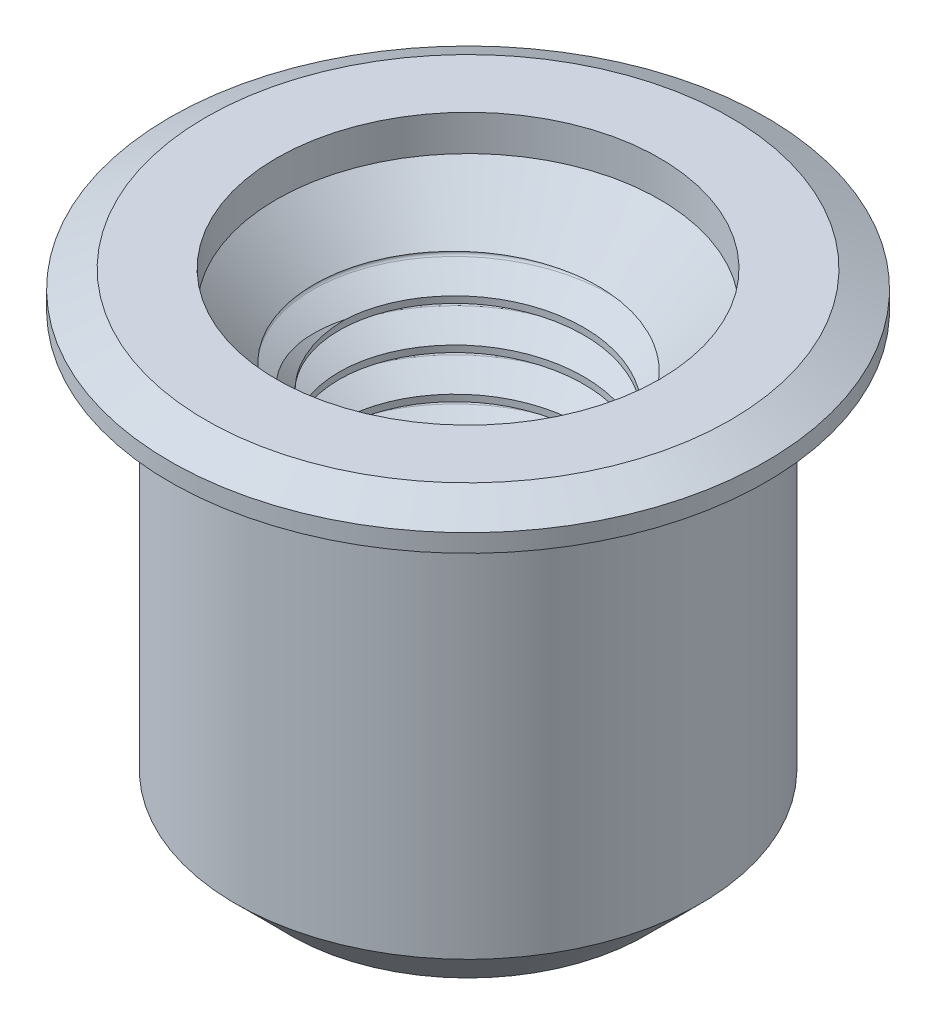
SolidWorks part; units mm, degrees
ref_plane "Front Plane" through (0, 0, 0) normal (0, 0, 1) x (1, 0, 0)
ref_plane "Top Plane" through (0, 0, 0) normal (0, 1, 0) x (1, 0, 0)
ref_plane "Right Plane" through (0, 0, 0) normal (1, 0, 0) x (0, 0, -1)
sketch "Sketch1" plane through (0, 0, 0) normal (0, 0, 1) x (1, 0, 0)
  line L0 (-4.953, -9.2415) -> (-3.7805, -10.414)
  line L1 (-4.0821, -0.762) -> (-2.608, -0.762) construction
  line L2 (-2.608, -0.762) -> (-2.608, -2.2361) construction
  line L3 (-3.7805, -10.414) -> (-3.175, -10.414)
  line L4 (6.35, 0) -> (5.588, 0) construction
  line L5 (-3.175, -10.414) -> (-2.608, -9.847)
  line L6 (6.35, -0.381) -> (6.35, 0) construction
  line L7 (-2.608, -9.847) -> (-2.608, -2.2361)
  line L8 (4.953, -10.414) -> (3.7805, -10.414) construction
  line L9 (-2.608, -2.2361) -> (-4.0821, -0.762)
  line L10 (2.608, -10.414) -> (2.608, -9.847) construction
  line L11 (-4.0821, -0.762) -> (-4.0821, 0)
  line L12 (4.953, -9.2415) -> (4.953, -10.414) construction
  line L13 (3.175, -10.414) -> (2.608, -10.414) construction
  line L14 (-4.0821, 0) -> (-5.588, 0)
  line L15 (-5.588, 0) -> (-6.35, -0.381)
  line L16 (6.35, -11.0998) -> (6.35, -1.4478) construction
  line L17 (-6.35, -0.381) -> (-6.35, -0.762)
  line L18 (6.35, -0.762) -> (4.953, -0.762) construction
  line L19 (-6.35, -0.762) -> (-4.953, -0.762)
  line L20 (-4.953, -0.762) -> (-4.953, -9.2415)
  line L21 (0, 0) -> (0, -10.414) construction
  line L22 (-6.35, -0.762) -> (-6.35, 0) construction
  line L23 (-6.35, 0) -> (-5.588, 0) construction
  line L24 (-4.953, -9.2415) -> (-4.953, -10.414) construction
  line L25 (-4.953, -10.414) -> (-3.7805, -10.414) construction
  line L26 (-3.175, -10.414) -> (-2.608, -10.414) construction
  line L27 (-2.608, -10.414) -> (-2.608, -9.847) construction
  line L28 (-2.608, -10.414) -> (0, -10.414) construction
  line L29 (6.35, -0.381) -> (6.35, -0.762) construction
  line L30 (-3.7805, -10.414) -> (-2.608, -10.414) construction
  line L32 (0, 0) -> (-4.0821, 0) construction
  dimension "D7" = 5.2161
  dimension "D8" = 45
  dimension "D12" = 9.652
  dimension "D2" = 8.1643
revolve "Revolve1" add sketch "Sketch1" angle 360 about L21
sketch "Sketch3" plane through (0, -10.414, 0) normal (0, -1, 0) x (1, 0, 0)
  circle A1 centre (0, 0) radius 3.175
  point P1 (3.175, 0)
  dimension "D1" = 6.35
ref_plane "Plane1" through (-4.953, 0, 0) normal (1, 0, 0) x (0, 0, -1)
sketch "Sketch2" plane through (-4.953, 0, 0) normal (1, 0, 0) x (0, 0, -1)
  line L0 (-4.953, -0.762) -> (4.953, -0.762) construction
  line L1 (-0.127, -0.762) -> (0.127, -0.762)
  line L2 (-0.127, -0.762) -> (-0.127, -0.254)
  line L3 (-0.127, -0.254) -> (0.127, -0.254) construction
  line L4 (0.127, -0.762) -> (0.127, -0.254)
  line L5 (0, -0.762) -> (0, 0) construction
  line L6 (-0.127, -0.254) -> (0, -0.762)
  line L7 (0, -0.762) -> (0.127, -0.254)
  line L8 (0, -0.254) -> (0, -0.762) construction
  line L10 (0, -0.762) -> (0, -0.254) construction
  line L11 (0, -0.508) -> (0, -0.254) construction
  dimension "D1" = 0.254
ref_axis "Axis1" through (0, 0, 0) along (0, -1, 0)
curve "Helix/Spiral1" pitch 0.9071 height 18.5388 radius 3.175 centre (0, -10.414, 0) axis (0, 1, 0) start towards (1, 0, 0) parameters "Height"=18.5388, "Pitch"=0.9071
sketch "Sketch4" plane through (0, 0, 0) normal (0, 0, 1) x (1, 0, 0)
  line L0 (2.4876, -10.0171) -> (2.4876, -10.9243) construction
  line L1 (2.4876, -10.9243) -> (3.2732, -10.4707) construction
  line L2 (2.4876, -10.0171) -> (3.2732, -10.4707) construction
  line L3 (2.5858, -10.0738) -> (2.5858, -10.8676) construction
  line L6 (2.4876, -10.4707) -> (2.5858, -10.4707) construction
  line L8 (3.175, -10.4707) -> (3.2732, -10.4707) construction
  line L9 (3.175, -10.414) -> (3.175, -10.5274) construction
  line L11 (2.5367, -10.0455) -> (2.5367, -10.8959)
  line L12 (2.5367, -10.8959) -> (3.175, -10.5274)
  line L14 (3.175, -10.414) -> (2.5367, -10.0455)
  arc A0 (3.175, -10.5274) -> (3.175, -10.414) centre (3.1423, -10.4707) ccw
  point P13 (2.5367, -10.4707)
  dimension "D1" = 0.9071
  dimension "D2" = 0.1134
sweep "Cut-Sweep1" cut profiles "Sketch4" path "Helix/Spiral1" align with end faces yes
ref_plane "Plane2" [suppressed] through (0, -2.794, 0) normal (0, -1, 0) x (1, 0, 0)
sketch "Sketch5" [suppressed] plane through (0, -2.794, 0) normal (0, -1, 0) x (1, 0, 0)
  circle A0 centre (0, 0) radius 3.429
  point P3 (-3.429, 0)
extrude "Extrude2" [suppressed] cut sketch "Sketch5" along normal blind 0.6858
pattern_linear "LPattern1" [suppressed] count 2 spacing 0.6858 along (0, 1, 0) of bodies 117
delete or keep bodies "Body-Delete1" [suppressed] type delete bodies bodies 117
combine bodies "Combine1" [suppressed] operation type add bodies to combine 118 119
sketch "Sketch6" [suppressed] plane through (0, 0, 0) normal (0, 0, 1) x (1, 0, 0)
  line L0 (-3.429, -2.794) -> (-2.8765, -2.794)
  line L1 (-2.8765, -2.794) -> (-2.8765, -4.318)
  line L2 (-2.8765, -4.318) -> (-3.429, -4.318)
  line L3 (-2.8765, -3.683) -> (-2.8765, 0) construction
  line L4 (-6.985, -2.794) -> (6.985, -2.794) construction
  line L5 (-3.429, -0.762) -> (-3.429, -10.5089) construction
  line L6 (0, 0) -> (0, -11.43) construction
  line L7 (0, 0) -> (0, -11.43) construction
  arc A0 (-3.429, -2.794) -> (-3.429, -4.318) centre (-3.429, -3.556) ccw
  dimension "D1" = 1.524
revolve "Revolve2" [suppressed] add sketch "Sketch6" angle 360 about L7
equation "\"Height@Helix/Spiral1\" = \"Body Lg@Sketch1\" + \"Pitch@Helix/Spiral1\" +  (  pi  / 10 ) "
equation "\"D1@Sketch4\" = \"Pitch@Helix/Spiral1\""
equation "\"D2@Sketch4\" = \"D1@Sketch4\" / 8"
equation "\"D1@Extrude2\" = \"D1@Sketch1\""
equation "\"D3@LPattern1\" = \"D1@Extrude2\""
equation "\"D7@Sketch1\" = \"Thread Dia@Sketch1\" -  ( \"Pitch@Helix/Spiral1\" )  * 1.25"
equation "\"D2@Sketch1\" =  \"Thread Dia@Sketch1\" + ( \"Pitch@Helix/Spiral1\" ) * 2"
equation "\"D12@Sketch1\" = \"Max Installed Lg@Sketch1\""
equation "\"D1@Sketch3\" = \"Thread Dia@Sketch1\""
